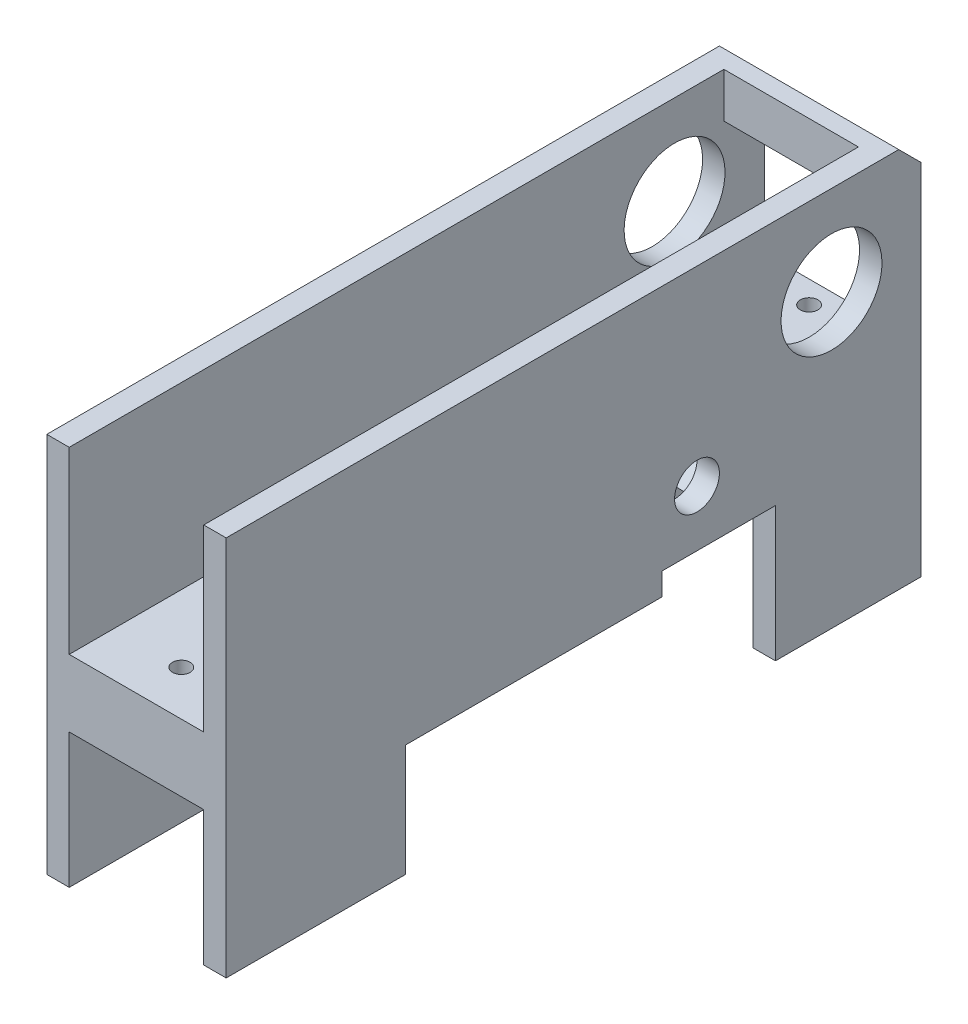
SolidWorks part; units mm, degrees
ref_plane "Front Plane" through (0, 0, 0) normal (0, 0, 1) x (1, 0, 0)
ref_plane "Top Plane" through (0, 0, 0) normal (0, 1, 0) x (1, 0, 0)
ref_plane "Right Plane" through (0, 0, 0) normal (1, 0, 0) x (0, 0, -1)
sketch "Sketch1" plane through (0, 0, 0) normal (0, 0, 1) x (1, 0, 0)
  line L0 (-25.4, -47.625) -> (-19.05, -47.625)
  line L1 (-19.05, -47.625) -> (-19.05, -9.525)
  line L2 (-19.05, -9.525) -> (19.05, -9.525)
  line L3 (19.05, -9.525) -> (19.05, -47.625)
  line L4 (19.05, -47.625) -> (25.4, -47.625)
  line L5 (25.4, -47.625) -> (25.4, 60.325)
  line L6 (25.4, 60.325) -> (19.05, 60.325)
  line L7 (19.05, 60.325) -> (19.05, 9.525)
  line L8 (19.05, 9.525) -> (-19.05, 9.525)
  line L9 (-19.05, 9.525) -> (-19.05, 60.325)
  line L10 (-19.05, 60.325) -> (-25.4, 60.325)
  line L11 (-25.4, 60.325) -> (-25.4, -47.625)
  line L12 (0, 9.525) -> (0, -9.525) construction
  line L14 (25.4, 0) -> (-25.4, 0) construction
  point P14 (0, 0)
  dimension "D1" = 38.1
  dimension "D2" = 6.35
  dimension "D3" = 50.8
  dimension "D4" = 38.1
  dimension "D5" = 19.05
extrude "Boss-Extrude1" add sketch "Sketch1" along normal mid plane 50.8
sketch "Sketch2" plane through (-25.4, 0, 0) normal (-1, 0, 0) x (0, 0, 1)
  line L0 (25.4, 9.525) -> (-25.4, 9.525) construction
  line L1 (25.4, 60.325) -> (25.4, -47.625) construction
  line L2 (-25.4, 60.325) -> (-25.4, -47.625) construction
  circle A0 centre (0, 34.925) radius 14.2875
  dimension "D1" = 28.575
  dimension "D2" = 9.525
  dimension "D3" = 25.4
extrude "Cut-Extrude1" cut sketch "Sketch2" against normal through all
sketch "Sketch3" plane through (0, 0, 25.4) normal (0, 0, -1) x (-1, 0, 0)
  line L0 (25.4, 60.325) -> (25.4, -47.625) construction
  line L1 (-25.4, -47.625) -> (25.4, -47.625)
  line L2 (-25.4, -47.625) -> (-25.4, -9.525)
  line L3 (-25.4, -9.525) -> (25.4, -9.525)
  line L4 (25.4, -47.625) -> (25.4, -9.525)
  line L5 (19.05, -9.525) -> (-19.05, -9.525) construction
extrude "Cut-Extrude3" cut sketch "Sketch3" along normal blind 9.525
sketch "Sketch4" plane through (19.05, 0, 0) normal (-1, 0, 0) x (0, 0, 1)
  line L1 (-25.4, 60.325) -> (-13.97, 60.325)
  line L2 (-25.4, 60.325) -> (-25.4, 47.625)
  line L3 (-25.4, 47.625) -> (-13.97, 47.625)
  line L4 (-13.97, 60.325) -> (-13.97, 47.625)
  dimension "D1" = 11.43
  dimension "D2" = 12.7
extrude "Boss-Extrude2" add sketch "Sketch4" along normal up to surface (38.1 mm away) up to face at (-19.05, 20.6375, 0)
chamfer "Chamfer1" distance 6.35 angle 45 1 edges at (0, 60.325, -25.4)
sketch "Sketch5" plane through (0, 0, 25.4) normal (0, 0, 1) x (1, 0, 0)
  line L0 (-25.4, 60.325) -> (-19.05, 60.325)
  line L4 (19.05, 60.325) -> (25.4, 60.325)
  line L5 (25.4, 60.325) -> (25.4, -9.525)
  line L7 (-25.4, -9.525) -> (-25.4, 60.325)
  line L12 (-19.05, 60.325) -> (-19.05, -9.525)
  line L13 (-25.4, -9.525) -> (25.4, -9.525) construction
  line L14 (-19.05, -9.525) -> (-25.4, -9.525)
  line L15 (19.05, 60.325) -> (19.05, -9.525)
  line L16 (19.05, -9.525) -> (25.4, -9.525)
extrude "Boss-Extrude3" add sketch "Sketch5" along normal blind 95.25
sketch "Sketch7" plane through (-25.4, 0, 0) normal (-1, 0, 0) x (0, 0, 1)
  circle A0 centre (38.1, 6.35) radius 6.35
  dimension "D1" = 12.7
  dimension "D2" = 6.35
  dimension "D3" = 38.1
extrude "Cut-Extrude5" cut sketch "Sketch7" against normal through all
sketch "Sketch8" plane through (0, 0, 25.4) normal (0, 0, 1) x (1, 0, 0)
  line L0 (19.05, 9.525) -> (19.05, -9.525) construction
  line L1 (-19.05, 9.525) -> (19.05, 9.525)
  line L2 (-19.05, 9.525) -> (-19.05, 0)
  line L3 (-19.05, 0) -> (19.05, 0)
  line L4 (19.05, 9.525) -> (19.05, 0)
extrude "Cut-Extrude6" cut sketch "Sketch8" against normal blind 9.525
chamfer "Chamfer4" distance 9.525 angle 45 1 edges at (0, 0, 25.4)
sketch "Sketch10" plane through (0, -9.525, 0) normal (0, -1, 0) x (1, 0, 0)
  line L0 (-25.4, 15.875) -> (-25.4, 120.65) construction
  line L1 (-25.4, 48.0088) -> (25.4, 48.0088)
  line L2 (-25.4, 48.0088) -> (-25.4, 120.65)
  line L3 (-25.4, 120.65) -> (25.4, 120.65)
  line L4 (25.4, 48.0088) -> (25.4, 120.65)
  line L5 (25.4, 15.875) -> (25.4, 120.65) construction
  line L6 (-25.4, 120.65) -> (-19.05, 120.65) construction
extrude "Boss-Extrude5" add sketch "Sketch10" along normal blind 6.35
sketch "Sketch12" plane through (0, 0, 120.65) normal (0, 0, 1) x (1, 0, 0)
  line L0 (-25.4, 60.325) -> (-19.05, 60.325)
  line L1 (-19.05, 60.325) -> (-19.05, 9.525)
  line L2 (-19.05, 9.525) -> (19.05, 9.525)
  line L3 (19.05, 9.525) -> (19.05, 60.325)
  line L4 (19.05, 60.325) -> (25.4, 60.325)
  line L5 (25.4, 60.325) -> (25.4, -47.625)
  line L6 (25.4, -47.625) -> (19.05, -47.625)
  line L7 (19.05, -47.625) -> (19.05, -15.875)
  line L8 (25.4, -15.875) -> (-25.4, -15.875) construction
  line L9 (19.05, -9.525) -> (19.05, -47.625) construction
  line L10 (19.05, -15.875) -> (-19.05, -15.875)
  line L11 (-19.05, -47.625) -> (-19.05, -9.525) construction
  line L12 (-19.05, -15.875) -> (-19.05, -47.625)
  line L13 (-19.05, -47.625) -> (-25.4, -47.625)
  line L14 (-25.4, -47.625) -> (-25.4, 60.325)
extrude "Boss-Extrude9" add sketch "Sketch12" along normal blind 50.8
sketch "Sketch13" plane through (0, -15.875, 0) normal (0, -1, 0) x (-1, 0, 0)
  line L0 (-19.05, -171.45) -> (-19.05, -120.65) construction
  line L1 (19.05, -171.45) -> (-19.05, -171.45)
  line L2 (19.05, -171.45) -> (19.05, -120.65)
  line L3 (19.05, -120.65) -> (-19.05, -120.65)
  line L4 (-19.05, -171.45) -> (-19.05, -120.65)
extrude "Cut-Extrude8" cut sketch "Sketch13" against normal blind 6.3754
sketch "Sketch14" plane through (0, -9.525, 0) normal (0, -1, 0) x (1, 0, 0)
  line L0 (-19.05, -25.4) -> (19.05, -25.4) construction
  circle A0 centre (0, -19.05) radius 2.4892
  circle A1 centre (0, 6.35) radius 2.4892
  dimension "D1" = 4.9784
  dimension "D2" = 6.35
  dimension "D3" = 25.4
extrude "Cut-Extrude9" cut sketch "Sketch14" against normal up to surface (19.05 mm away) up to face at (0, 9.525, -4.7625)
sketch "Sketch15" plane through (0, -9.4996, 0) normal (0, -1, 0) x (1, 0, 0)
  line L0 (19.05, 171.45) -> (-19.05, 171.45) construction
  line L1 (-25.4, 158.75) -> (25.4, 158.75) construction
  line L2 (-25.4, 171.45) -> (-25.4, 120.65) construction
  line L3 (25.4, 171.45) -> (25.4, 120.65) construction
  circle A0 centre (0, 158.75) radius 2.4892
  circle A1 centre (0, 133.35) radius 2.4892
  circle A2 centre (0, 6.35) radius 2.4892 construction
  point P14 (0, 0)
  dimension "D1" = 12.7
  dimension "D2" = 25.4
extrude "Cut-Extrude10" cut sketch "Sketch15" against normal up to surface (19.0246 mm away) up to face at (0, 9.525, 146.05)
